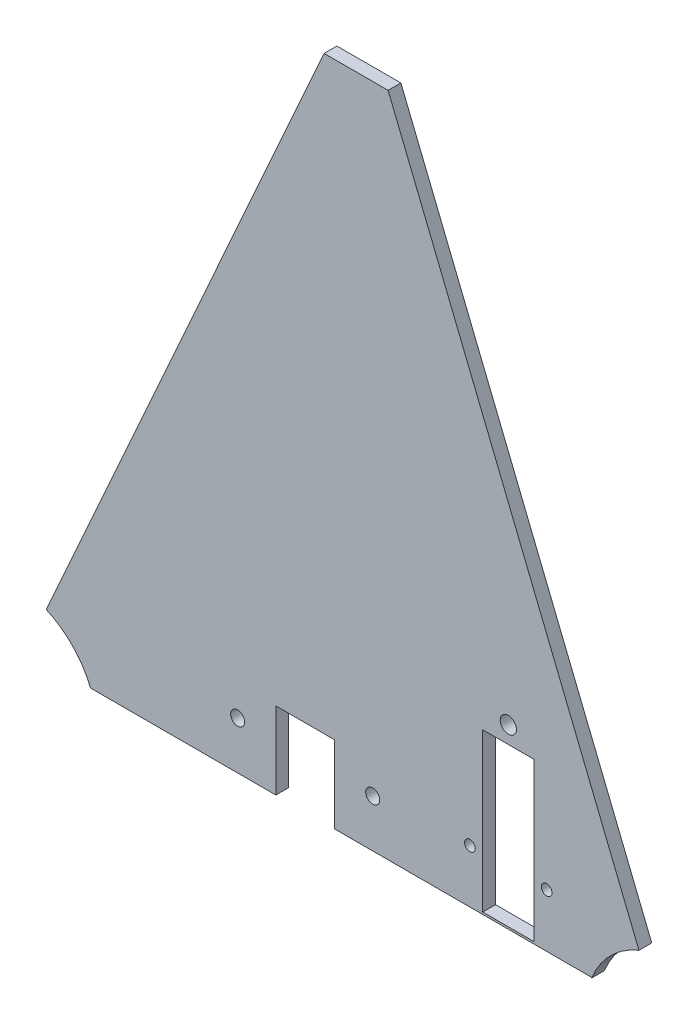
SolidWorks part; units mm, degrees
ref_plane "Front Plane" through (0, 0, 0) normal (0, 0, 1) x (1, 0, 0)
ref_plane "Top Plane" through (0, 0, 0) normal (0, 1, 0) x (1, 0, 0)
ref_plane "Right Plane" through (0, 0, 0) normal (1, 0, 0) x (0, 0, -1)
sketch "Sketch2" plane through (0, 0, 0) normal (0, 0, 1) x (1, 0, 0)
  line L0 (-189.7401, 245.3834) -> (-375.9085, -170.4146)
  line L1 (-375.9085, -170.4146) -> (16.7755, -170.4146)
  line L2 (16.7755, -170.4146) -> (-151.6401, 245.3834)
  line L4 (-189.7401, 245.3834) -> (-151.6401, 245.3834)
  dimension "D1" = 415.798
  dimension "D2" = 415.798
  dimension "D3" = 67.95
  dimension "D4" = 38.1
  dimension "D5" = 392.684
extrude "Boss-Extrude1" add sketch "Sketch2" along normal blind 7.62 contours L0 L1 L2 L4
sketch "Sketch5" plane through (0, 0, 0) normal (0, 0, -1) x (-1, 0, 0)
  circle A0 centre (375.9085, -170.4146) radius 15.875
  dimension "D1" = 31.75
extrude "Cut-Extrude2" cut sketch "Sketch5" against normal blind 50.8
sketch "Sketch6" plane through (0, 0, 0) normal (0, 0, -1) x (-1, 0, 0)
  circle A0 centre (-16.7755, -170.4146) radius 15.875
  dimension "D1" = 31.75
extrude "Cut-Extrude3" cut sketch "Sketch6" against normal blind 50.8 contours A0
ref_plane "Plane1" through (-360.0335, -170.4146, 0) normal (1, 0, 0) x (0, 0, -1)
sketch "Sketch8" plane through (0, 0, 0) normal (0, 0, -1) x (-1, 0, 0)
  line L0 (254.9716, -43.4146) -> (147.0216, -43.4146) construction
  line L1 (360.0335, -170.4146) -> (-0.9005, -170.4146) construction
  line L2 (254.9716, -170.4146) -> (254.9716, 97.7332) construction
  line L3 (254.9716, -43.4146) -> (254.9716, -170.4146) construction
  line L4 (147.0216, -43.4146) -> (147.0216, -170.4146) construction
  line L5 (147.0216, -170.4146) -> (183.5239, -170.4146) construction
  line L6 (183.5239, -170.4146) -> (183.5239, -105.3906) construction
  line L7 (170.6901, 245.3834) -> (179.5665, -170.4146) construction
  line L8 (189.7401, 245.3834) -> (151.6401, 245.3834) construction
  line L9 (183.5239, -105.3906) -> (218.4489, -105.3906) construction
  line L10 (218.4489, -105.3906) -> (218.4489, -170.4146) construction
  line L11 (218.4489, -170.4146) -> (218.4489, -105.3906)
  line L12 (218.4489, -105.3906) -> (183.5239, -105.3906)
  line L13 (183.5239, -105.3906) -> (183.5239, -170.4146)
  line L14 (153.8492, -170.4146) -> (153.8492, -48.647) construction
  dimension "D1" = 268.1478
  dimension "D2" = 107.95
  dimension "D3" = 127
  dimension "D4" = 36.5023
  dimension "D5" = 65.024
  dimension "D6" = 34.925
  dimension "D7" = 121.7676
extrude "Cut-Extrude4" cut sketch "Sketch8" against normal blind 7.62 and the other way through all contours L11 L12 L13
sketch "Sketch9" plane through (0, 0, 0) normal (0, 0, -1) x (-1, 0, 0)
  line L0 (164.9819, -123.0436) -> (183.5239, -123.0436) construction
  line L1 (183.5239, -170.4146) -> (183.5239, -105.3906) construction
  line L2 (160.7909, -127.2346) -> (160.7909, -170.4146) construction
  line L3 (183.5239, -170.4146) -> (-0.9005, -170.4146) construction
  line L4 (236.9909, -123.0436) -> (218.4489, -123.0436) construction
  line L5 (218.4489, -105.3906) -> (218.4489, -170.4146) construction
  line L6 (241.1819, -127.2346) -> (241.1819, -170.4146) construction
  line L7 (360.0335, -170.4146) -> (218.4489, -170.4146) construction
  circle A0 centre (160.7909, -123.0436) radius 4.191
  circle A1 centre (241.1819, -123.0436) radius 4.191
  dimension "D3" = 8.382
  dimension "D6" = 8.382
  dimension "D1" = 18.542
  dimension "D2" = 43.18
  dimension "D4" = 18.542
  dimension "D5" = 43.18
sketch "Sketch10" plane through (0, 0, 0) normal (0, 0, -1) x (-1, 0, 0)
  line L0 (218.4489, -110.7541) -> (349.1963, -110.7541) construction
  line L1 (218.4489, -105.3906) -> (218.4489, -170.4146) construction
  line L2 (189.7401, 245.3834) -> (369.4213, -155.9256) construction
  line L3 (7.3895, -110.7541) -> (138.1995, -110.7541) construction
  line L4 (-10.8158, -155.7008) -> (151.6401, 245.3834) construction
  line L5 (64.8263, -170.4146) -> (64.8263, -56.1146) construction
  line L8 (183.5239, -170.4146) -> (-0.9005, -170.4146) construction
  line L9 (64.8263, -56.1146) -> (95.3063, -56.1146) construction
  line L11 (95.3063, -56.1146) -> (95.3063, -170.4146) construction
  line L12 (64.8263, -170.4146) -> (64.8263, -56.1146)
  line L13 (64.8263, -56.1146) -> (95.3063, -56.1146)
  line L14 (95.3063, -56.1146) -> (95.3063, -170.4146)
  line L15 (64.8263, -170.4146) -> (95.3063, -170.4146)
  dimension "D1" = 130.7473
  dimension "D2" = 130.81
  dimension "D3" = 114.3
  dimension "D4" = 30.48
extrude "Cut-Extrude6" cut sketch "Sketch9" against normal up to next
extrude "Cut-Extrude12" cut sketch "Sketch10" against normal blind 25.4 contours L13 L14 L15 L12
sketch "Sketch13" plane through (0, 0, 0) normal (0, 0, -1) x (-1, 0, 0)
  line L0 (80.0663, -56.1146) -> (80.0663, -50.7806) construction
  line L1 (64.8263, -56.1146) -> (95.3063, -56.1146) construction
  line L2 (80.0663, -50.7806) -> (80.0663, -45.9546) construction
  circle A0 centre (80.0663, -45.9546) radius 4.826
  dimension "D3" = 9.652
  dimension "D1" = 5.334
  dimension "D2" = 4.826
extrude "Cut-Extrude13" cut sketch "Sketch13" against normal up to next
sketch "Sketch14" plane through (0, 0, 0) normal (0, 0, -1) x (-1, 0, 0)
  circle A0 centre (-16.7755, -170.4146) radius 50.8
  dimension "D1" = 101.6
extrude "Cut-Extrude14" cut sketch "Sketch14" against normal up to next
sketch "Sketch15" plane through (0, 0, 0) normal (0, 0, -1) x (-1, 0, 0)
  circle A0 centre (375.9085, -170.4146) radius 50.8
  dimension "D1" = 101.6
extrude "Cut-Extrude15" cut sketch "Sketch15" against normal up to next
sketch "Sketch16" plane through (0, 0, 0) normal (0, 0, -1) x (-1, 0, 0)
  line L0 (95.3063, -56.1146) -> (95.3063, -170.4146) construction
  line L1 (95.3063, -150.0946) -> (64.8263, -150.0946)
  line L2 (95.3063, -150.0946) -> (95.3063, -170.4146)
  line L3 (95.3063, -170.4146) -> (64.8263, -170.4146)
  line L4 (64.8263, -150.0946) -> (64.8263, -170.4146)
  dimension "D1" = 20.32
extrude "Boss-Extrude2" add sketch "Sketch16" against normal blind 7.62
sketch "Sketch17" plane through (0, 0, 0) normal (0, 0, -1) x (-1, 0, 0)
  line L0 (64.8263, -150.0946) -> (64.8263, -125.9646) construction
  line L1 (64.8263, -150.0946) -> (64.8263, -56.1146) construction
  line L2 (64.8263, -125.9646) -> (64.8263, -113.2646) construction
  line L3 (64.8263, -113.2646) -> (49.5863, -113.2646) construction
  line L4 (49.5863, -113.2646) -> (49.5863, -125.9646) construction
  line L5 (49.5863, -125.9646) -> (64.8263, -125.9646) construction
  line L6 (49.5863, -119.6146) -> (64.8263, -119.6146) construction
  line L7 (95.3063, -113.2646) -> (110.5463, -113.2646) construction
  line L8 (95.3063, -56.1146) -> (95.3063, -150.0946) construction
  line L9 (110.5463, -113.2646) -> (110.5463, -125.9646) construction
  line L10 (110.5463, -125.9646) -> (95.3063, -125.9646) construction
  line L11 (110.5463, -119.6146) -> (95.3063, -119.6146) construction
  circle A0 centre (57.2063, -119.6146) radius 3.175
  circle A3 centre (102.9263, -119.6146) radius 3.175
  dimension "D4" = 6.35
  dimension "D7" = 6.35
  dimension "D1" = 24.13
  dimension "D2" = 12.7
  dimension "D3" = 15.24
  dimension "D5" = 15.24
  dimension "D6" = 12.7
extrude "Cut-Extrude16" cut sketch "Sketch17" against normal up to next
sketch "Sketch18" plane through (0, 0, 0) normal (0, 0, -1) x (-1, 0, 0)
  line L5 (30.4451, -170.4146) -> (331.0546, -170.4146)
  line L6 (30.4451, -170.4146) -> (30.4451, -151.3646)
  line L7 (30.4451, -151.3646) -> (331.0546, -151.3646)
  line L8 (331.0546, -170.4146) -> (331.0546, -151.3646)
  dimension "D1" = 19.05
extrude "Cut-Extrude17" cut sketch "Sketch18" against normal up to next (7.62 mm away) contours L7 L8 L5 L6
